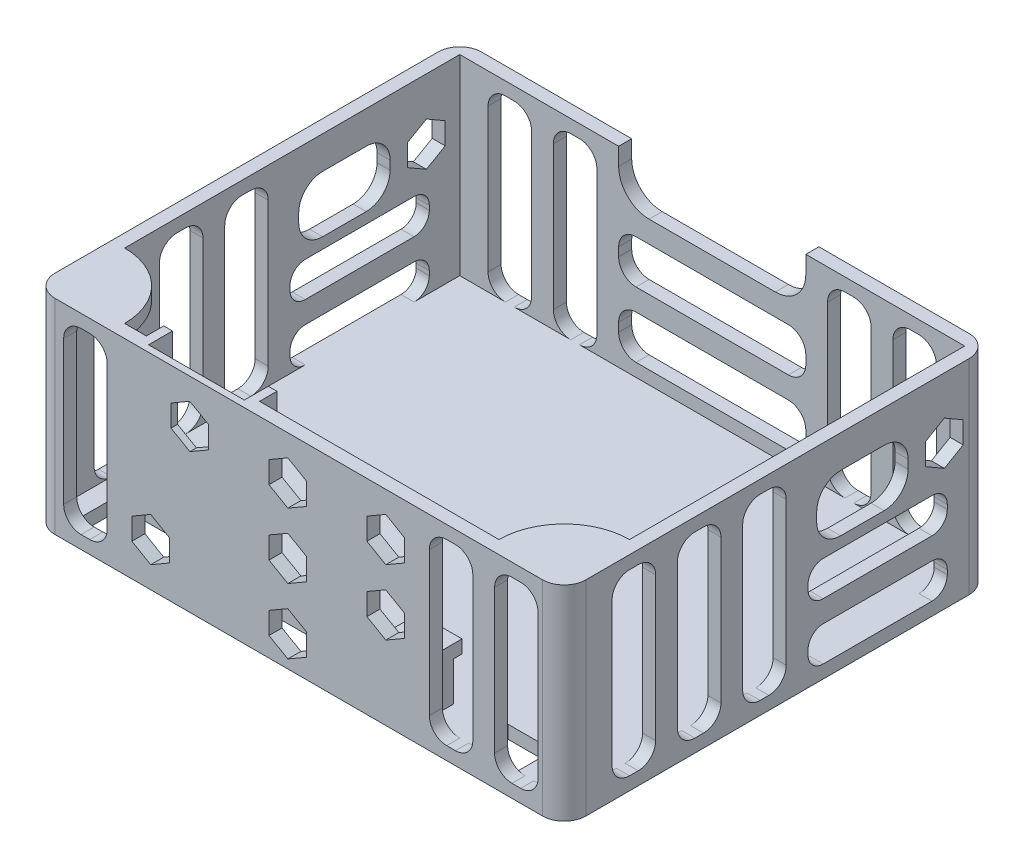
SolidWorks part; units mm, degrees
ref_plane "Front Plane" through (0, 0, 0) normal (0, 0, 1) x (1, 0, 0)
ref_plane "Top Plane" through (0, 0, 0) normal (0, 1, 0) x (1, 0, 0)
ref_plane "Right Plane" through (0, 0, 0) normal (1, 0, 0) x (0, 0, -1)
sketch "Sketch1" plane through (0, 0, 0) normal (0, 1, 0) x (1, 0, 0)
  line L1 (-81.2987, -43.7828) -> (-20.2987, -43.7828)
  line L2 (-81.2987, -43.7828) -> (-81.2987, 5.2172)
  line L3 (-81.2987, 5.2172) -> (-20.2987, 5.2172)
  line L4 (-20.2987, -43.7828) -> (-20.2987, 5.2172)
  dimension "D1" = 61
  dimension "D2" = 49
extrude "Boss-Extrude1" add sketch "Sketch1" along normal blind 23.5
sketch "Sketch2" plane through (0, 23.5, 0) normal (0, 1, 0) x (1, 0, 0)
  line L0 (-81.2987, 5.2172) -> (-81.2987, -43.7828) construction
  line L1 (-79.7987, 3.7172) -> (-21.7987, 3.7172)
  line L2 (-79.7987, 3.7172) -> (-79.7987, -42.2828)
  line L3 (-79.7987, -42.2828) -> (-21.7987, -42.2828)
  line L4 (-21.7987, 3.7172) -> (-21.7987, -42.2828)
  line L5 (-81.2987, -43.7828) -> (-20.2987, -43.7828) construction
  line L6 (-20.2987, -43.7828) -> (-20.2987, 5.2172) construction
  line L7 (-20.2987, 5.2172) -> (-81.2987, 5.2172) construction
  dimension "D1" = 1.5
  dimension "D2" = 1.5
  dimension "D3" = 1.5
  dimension "D4" = 1.5
extrude "Cut-Extrude1" cut sketch "Sketch2" against normal blind 22
sketch "Sketch3" plane through (0, 1.5, 0) normal (0, 1, 0) x (1, 0, 0)
  line L0 (-79.7987, -42.2828) -> (-21.7987, -42.2828) construction
  line L1 (-58.5387, -39.2828) -> (-42.5387, -39.2828)
  line L2 (-58.5387, -39.2828) -> (-58.5387, -42.2828)
  line L3 (-58.5387, -42.2828) -> (-42.5387, -42.2828)
  line L4 (-42.5387, -39.2828) -> (-42.5387, -42.2828)
  line L5 (-21.7987, -42.2828) -> (-21.7987, 3.7172) construction
  line L6 (-32.3987, -38.1328) -> (-27.1987, -38.1328)
  line L7 (-32.3987, -38.1328) -> (-32.3987, -42.2828)
  line L8 (-32.3987, -42.2828) -> (-27.1987, -42.2828)
  line L9 (-27.1987, -38.1328) -> (-27.1987, -42.2828)
  line L10 (-65.5387, -37.2828) -> (-77.5387, -37.2828)
  line L11 (-65.5387, -37.2828) -> (-65.5387, -42.2828)
  line L12 (-65.5387, -42.2828) -> (-77.5387, -42.2828)
  line L13 (-77.5387, -37.2828) -> (-77.5387, -42.2828)
  dimension "D1" = 3
  dimension "D2" = 5.4
  dimension "D3" = 5.2
  dimension "D4" = 10.14
  dimension "D5" = 4.15
  dimension "D6" = 7
  dimension "D7" = 12
  dimension "D8" = 16
  dimension "D9" = 5
extrude "Cut-Extrude2" cut sketch "Sketch3" against normal blind 1.5
sketch "Sketch4" plane through (0, 23.5, 0) normal (0, 1, 0) x (1, 0, 0)
  line L0 (-20.2987, 5.2172) -> (-81.2987, 5.2172) construction
  line L1 (-61.5487, 5.2172) -> (-40.0487, 5.2172)
  line L2 (-61.5487, 5.2172) -> (-61.5487, 3.7172)
  line L3 (-61.5487, 3.7172) -> (-40.0487, 3.7172)
  line L4 (-40.0487, 5.2172) -> (-40.0487, 3.7172)
  line L5 (-21.7987, 3.7172) -> (-79.7987, 3.7172) construction
  dimension "D1" = 18.25
  dimension "D2" = 18.25
extrude "Cut-Extrude3" cut sketch "Sketch4" against normal blind 5.5
sketch "Sketch5" plane through (-81.2987, 0, 0) normal (-1, 0, 0) x (0, 0, 1)
  line L0 (-5.2172, 23.5) -> (43.7828, 23.5) construction
  line L1 (4.2828, 19.75) -> (14.7828, 19.75)
  line L2 (4.2828, 19.75) -> (4.2828, 13.25)
  line L3 (4.2828, 13.25) -> (14.7828, 13.25)
  line L4 (14.7828, 19.75) -> (14.7828, 13.25)
  dimension "D1" = 10.5
  dimension "D2" = 6.5
  dimension "D3" = 3.75
  dimension "D4" = 8
extrude "Cut-Extrude6" cut sketch "Sketch5" against normal blind 61
sketch "Sketch8" plane through (0, 1.5, 0) normal (0, 1, 0) x (1, 0, 0)
  line L0 (-42.5387, -42.2828) -> (-32.3987, -42.2828) construction
  line L1 (-37.5387, -42.2828) -> (-42.5387, -42.2828)
  line L2 (-37.5387, -42.2828) -> (-37.5387, -39.2828)
  line L3 (-37.5387, -39.2828) -> (-42.5387, -39.2828)
  line L4 (-42.5387, -42.2828) -> (-42.5387, -39.2828)
  line L6 (-58.5387, -42.2828) -> (-63.5387, -42.2828)
  line L7 (-58.5387, -42.2828) -> (-58.5387, -39.2828)
  line L8 (-58.5387, -39.2828) -> (-63.5387, -39.2828)
  line L9 (-63.5387, -42.2828) -> (-63.5387, -39.2828)
  dimension "D1" = 5
  dimension "D2" = 5
extrude "Boss-Extrude2" add sketch "Sketch8" along normal blind 6
sketch "Sketch9" plane through (0, 0, 39.2828) normal (0, 0, -1) x (-1, 0, 0)
  line L0 (37.5387, 7.5) -> (42.5387, 7.5) construction
  line L1 (37.5387, 7.5) -> (42.5387, 7.5)
  line L2 (37.5387, 7.5) -> (37.5387, 6)
  line L3 (37.5387, 6) -> (42.5387, 6)
  line L4 (42.5387, 7.5) -> (42.5387, 6)
  line L5 (42.5387, 7.5) -> (42.5387, 1.5) construction
  line L6 (58.5387, 7.5) -> (63.5387, 7.5) construction
  line L7 (58.5387, 7.5) -> (63.5387, 7.5)
  line L8 (58.5387, 7.5) -> (58.5387, 6)
  line L9 (58.5387, 6) -> (63.5387, 6)
  line L10 (63.5387, 7.5) -> (63.5387, 6)
  line L11 (63.5387, 7.5) -> (63.5387, 1.5) construction
  dimension "D1" = 1.5
  dimension "D2" = 1.5
extrude "Boss-Extrude3" add sketch "Sketch9" along normal blind 1
sketch "Sketch10" plane through (0, 0, 42.2828) normal (0, 0, -1) x (-1, 0, 0)
  line L0 (79.7987, 23.5) -> (21.7987, 23.5) construction
  line L1 (57.7987, 23.5) -> (68.7987, 23.5)
  line L2 (57.7987, 23.5) -> (57.7987, 12.5)
  line L3 (57.7987, 12.5) -> (68.7987, 12.5)
  line L4 (68.7987, 23.5) -> (68.7987, 12.5)
  line L5 (79.7987, 1.5) -> (79.7987, 23.5) construction
  dimension "D1" = 11
  dimension "D2" = 11
  dimension "D3" = 0
  dimension "D4" = 11
extrude "Cut-Extrude8" cut sketch "Sketch10" against normal blind 0.75
sketch "Sketch11" plane through (0, 0, 42.2828) normal (0, 0, -1) x (-1, 0, 0)
  line L1 (57.7987, 23.5) -> (56.7987, 23.5)
  line L2 (57.7987, 23.5) -> (57.7987, 11.5)
  line L3 (57.7987, 11.5) -> (56.7987, 11.5)
  line L4 (56.7987, 23.5) -> (56.7987, 11.5)
  line L5 (68.7987, 12.5) -> (57.7987, 12.5)
  line L6 (68.7987, 12.5) -> (68.7987, 11.5)
  line L7 (68.7987, 11.5) -> (57.7987, 11.5)
  line L8 (57.7987, 12.5) -> (57.7987, 11.5)
  line L9 (68.7987, 23.5) -> (69.7987, 23.5)
  line L10 (68.7987, 23.5) -> (68.7987, 11.5)
  line L11 (68.7987, 11.5) -> (69.7987, 11.5)
  line L12 (69.7987, 23.5) -> (69.7987, 11.5)
  line M8 (68.7987, 12.5) -> (57.7987, 12.5)
  line M30 (79.7987, 23.5) -> (68.7987, 23.5)
  line M31 (68.7987, 23.5) -> (68.7987, 12.5)
  dimension "D1" = 1
  dimension "D2" = 1
  dimension "D3" = 1
  dimension "D4" = 0
extrude "Boss-Extrude4" add sketch "Sketch11" along normal blind 2 contours L7 L6 L2 M8 | L12 L6 L11 M30 M31
sketch "Sketch12" plane through (0, 23.5, 0) normal (0, 1, 0) x (1, 0, 0)
  line L1 (-21.7987, -42.2828) -> (-29.2987, -42.2828)
  line L2 (-21.7987, -42.2828) -> (-21.7987, -34.7828)
  line L3 (-21.7987, -34.7828) -> (-29.2987, -34.7828)
  line L4 (-29.2987, -42.2828) -> (-29.2987, -34.7828)
  line L5 (-79.7987, -42.2828) -> (-72.2987, -42.2828)
  line L6 (-79.7987, -42.2828) -> (-79.7987, -34.7828)
  line L7 (-79.7987, -34.7828) -> (-72.2987, -34.7828)
  line L8 (-72.2987, -42.2828) -> (-72.2987, -34.7828)
  dimension "D1" = 7.5
  dimension "D2" = 7.5
  dimension "D3" = 7.5
  dimension "D4" = 7.5
extrude "Boss-Extrude5" add sketch "Sketch12" against normal blind 1.5
fillet "Fillet1" radius 2.75 1 edges at (-80.5487, 13.25, 14.7828)
fillet "Fillet2" radius 2.75 1 edges at (-80.5487, 19.75, 14.7828)
fillet "Fillet3" radius 2.75 1 edges at (-80.5487, 19.75, 4.2828)
fillet "Fillet4" radius 2.75 1 edges at (-80.5487, 13.25, 4.2828)
fillet "Fillet5" radius 3.5 1 edges at (-40.0487, 18, -4.4672)
fillet "Fillet6" radius 3.5 1 edges at (-61.5487, 18, -4.4672)
fillet "Fillet7" radius 7.5 5 edges at (-29.2987, 22, 38.5328) (-25.5487, 22, 34.7828) (-29.2987, 22.75, 34.7828) (-25.5487, 23.5, 34.7828) (-29.2987, 23.5, 38.5328)
fillet "Fillet8" radius 7.5 5 edges at (-76.0487, 22, 34.7828) (-72.2987, 22, 38.5328) (-72.2987, 22.75, 34.7828) (-72.2987, 23.5, 38.5328) (-76.0487, 23.5, 34.7828)
fillet "Fillet9" radius 2.5 1 edges at (-20.2987, 11.75, -5.2172)
fillet "Fillet10" radius 2.5 1 edges at (-81.2987, 11.75, -5.2172)
fillet "Fillet11" radius 2.5 1 edges at (-81.2987, 11.75, 43.7828)
fillet "Fillet12" radius 2.5 1 edges at (-20.2987, 11.75, 43.7828)
sketch "Sketch13" plane through (-20.2987, 0, 0) normal (1, 0, 0) x (0, 0, -1)
  line L0 (-41.2828, 23.5) -> (2.7172, 23.5) construction
  line L1 (-36.2828, 22) -> (-35.2828, 22)
  line L2 (-38.2828, 20) -> (-38.2828, 3.5)
  line L3 (-36.2828, 1.5) -> (-35.2828, 1.5)
  line L4 (-33.2828, 20) -> (-33.2828, 3.5)
  line L5 (-28.7828, 22) -> (-27.7828, 22)
  line L6 (-30.7828, 20) -> (-30.7828, 3.5)
  line L7 (-28.7828, 1.5) -> (-27.7828, 1.5)
  line L8 (-25.7828, 20) -> (-25.7828, 3.5)
  line L9 (-21.2828, 22) -> (-20.2828, 22)
  line L10 (-23.2828, 20) -> (-23.2828, 3.5)
  line L11 (-21.2828, 1.5) -> (-20.2828, 1.5)
  line L12 (-18.2828, 20) -> (-18.2828, 3.5)
  line L17 (-41.2828, 0) -> (2.7172, 0) construction
  line L18 (-38.2828, 7.5) -> (-38.2828, 6) construction
  arc A0 (-36.2828, 22) -> (-38.2828, 20) centre (-36.2828, 20) ccw
  arc A1 (-35.2828, 22) -> (-33.2828, 20) centre (-35.2828, 20) cw
  arc A2 (-28.7828, 22) -> (-30.7828, 20) centre (-28.7828, 20) ccw
  arc A3 (-27.7828, 22) -> (-25.7828, 20) centre (-27.7828, 20) cw
  arc A4 (-21.2828, 22) -> (-23.2828, 20) centre (-21.2828, 20) ccw
  arc A5 (-20.2828, 22) -> (-18.2828, 20) centre (-20.2828, 20) cw
  arc A6 (-20.2828, 1.5) -> (-18.2828, 3.5) centre (-20.2828, 3.5) ccw
  arc A7 (-23.2828, 3.5) -> (-21.2828, 1.5) centre (-21.2828, 3.5) ccw
  arc A8 (-27.7828, 1.5) -> (-25.7828, 3.5) centre (-27.7828, 3.5) ccw
  arc A9 (-30.7828, 3.5) -> (-28.7828, 1.5) centre (-28.7828, 3.5) ccw
  arc A10 (-35.2828, 1.5) -> (-33.2828, 3.5) centre (-35.2828, 3.5) ccw
  arc A11 (-38.2828, 3.5) -> (-36.2828, 1.5) centre (-36.2828, 3.5) ccw
  point P14 (-38.2828, 22)
  point P23 (-33.2828, 22)
  point P26 (-30.7828, 22)
  point P29 (-25.7828, 22)
  point P32 (-23.2828, 22)
  point P35 (-18.2828, 22)
  dimension "D4" = 2
  dimension "D1" = 5
  dimension "D2" = 5
  dimension "D3" = 5
  dimension "D5" = 2.5
  dimension "D6" = 2.5
  dimension "D8" = 1.5
  dimension "D9" = 1.5
  dimension "D10" = 1.5
  dimension "D12" = 1.5
  dimension "D13" = 1.5
  dimension "D14" = 1.5
  dimension "D16" = 0
extrude "Cut-Extrude10" cut sketch "Sketch13" against normal blind 61
fillet "Fillet13" radius 2.75 1 edges at (-21.0487, 13.25, 14.7828)
fillet "Fillet14" radius 2.75 1 edges at (-21.0487, 19.75, 14.7828)
fillet "Fillet15" radius 2.75 1 edges at (-21.0487, 13.25, 4.2828)
fillet "Fillet16" radius 2.75 1 edges at (-21.0487, 19.75, 4.2828)
sketch "Sketch16" plane through (-20.2987, 0, 0) normal (1, 0, 0) x (0, 0, -1)
  line L0 (-4.2828, 17) -> (-4.2828, 16) construction
  line L1 (-0.1178, 19) -> (-2.2828, 17.75)
  line L2 (-2.2828, 17.75) -> (-2.2828, 15.25)
  line L3 (-2.2828, 15.25) -> (-0.1178, 14)
  line L4 (-0.1178, 14) -> (2.0473, 15.25)
  line L5 (2.0473, 15.25) -> (2.0473, 17.75)
  line L6 (2.0473, 17.75) -> (-0.1178, 19)
  circle A0 centre (-0.1178, 16.5) radius 2.1651 construction
  point P10 (-4.2828, 16.5)
  dimension "D1" = 0
  dimension "D2" = 2.5
  dimension "D3" = 2
extrude "Cut-Extrude11" cut sketch "Sketch16" against normal blind 61
sketch "Sketch19" plane through (0, 0, -5.2172) normal (0, 0, -1) x (-1, 0, 0)
  line L0 (61.5487, 23.5) -> (78.7987, 23.5) construction
  line L1 (66.0487, 22) -> (67.0487, 22)
  line L2 (64.0487, 20) -> (64.0487, 3.5)
  line L3 (66.0487, 1.5) -> (67.0487, 1.5)
  line L4 (69.0487, 20) -> (69.0487, 3.5)
  line L5 (73.5487, 22) -> (74.5487, 22)
  line L6 (71.5487, 20) -> (71.5487, 3.5)
  line L7 (73.5487, 1.5) -> (74.5487, 1.5)
  line L8 (76.5487, 20) -> (76.5487, 3.5)
  line L9 (27.0487, 22) -> (28.0487, 22)
  line L10 (25.0487, 20) -> (25.0487, 3.5)
  line L11 (27.0487, 1.5) -> (28.0487, 1.5)
  line L12 (30.0487, 20) -> (30.0487, 3.5)
  line L13 (34.5487, 22) -> (35.5487, 22)
  line L14 (32.5487, 20) -> (32.5487, 3.5)
  line L15 (34.5487, 1.5) -> (35.5487, 1.5)
  line L16 (37.5487, 20) -> (37.5487, 3.5)
  line L17 (42.0487, 15.5) -> (59.5487, 15.5)
  line L18 (40.0487, 13.5) -> (40.0487, 12.5)
  line L19 (42.0487, 10.5) -> (59.5487, 10.5)
  line L20 (61.5487, 13.5) -> (61.5487, 12.5)
  line L21 (42.0487, 8) -> (59.5487, 8)
  line L22 (40.0487, 6) -> (40.0487, 5)
  line L23 (42.0487, 3) -> (59.5487, 3)
  line L24 (61.5487, 6) -> (61.5487, 5)
  line L25 (22.7987, 0) -> (78.7987, 0) construction
  line L26 (61.5487, 21.5) -> (61.5487, 23.5) construction
  line L27 (40.0487, 21.5) -> (40.0487, 23.5) construction
  line L28 (22.7987, 23.5) -> (40.0487, 23.5) construction
  line L29 (43.5487, 18) -> (58.0487, 18) construction
  arc A0 (25.0487, 3.5) -> (27.0487, 1.5) centre (27.0487, 3.5) ccw
  arc A1 (28.0487, 1.5) -> (30.0487, 3.5) centre (28.0487, 3.5) ccw
  arc A2 (32.5487, 3.5) -> (34.5487, 1.5) centre (34.5487, 3.5) ccw
  arc A3 (35.5487, 1.5) -> (37.5487, 3.5) centre (35.5487, 3.5) ccw
  arc A4 (42.0487, 8) -> (40.0487, 6) centre (42.0487, 6) ccw
  arc A5 (40.0487, 5) -> (42.0487, 3) centre (42.0487, 5) ccw
  arc A6 (59.5487, 8) -> (61.5487, 6) centre (59.5487, 6) cw
  arc A7 (59.5487, 3) -> (61.5487, 5) centre (59.5487, 5) ccw
  arc A8 (64.0487, 3.5) -> (66.0487, 1.5) centre (66.0487, 3.5) ccw
  arc A9 (67.0487, 1.5) -> (69.0487, 3.5) centre (67.0487, 3.5) ccw
  arc A10 (71.5487, 3.5) -> (73.5487, 1.5) centre (73.5487, 3.5) ccw
  arc A11 (74.5487, 1.5) -> (76.5487, 3.5) centre (74.5487, 3.5) ccw
  arc A12 (74.5487, 22) -> (76.5487, 20) centre (74.5487, 20) cw
  arc A13 (73.5487, 22) -> (71.5487, 20) centre (73.5487, 20) ccw
  arc A14 (67.0487, 22) -> (69.0487, 20) centre (67.0487, 20) cw
  arc A15 (66.0487, 22) -> (64.0487, 20) centre (66.0487, 20) ccw
  arc A16 (59.5487, 15.5) -> (61.5487, 13.5) centre (59.5487, 13.5) cw
  arc A17 (59.5487, 10.5) -> (61.5487, 12.5) centre (59.5487, 12.5) ccw
  arc A18 (40.0487, 12.5) -> (42.0487, 10.5) centre (42.0487, 12.5) ccw
  arc A19 (42.0487, 15.5) -> (40.0487, 13.5) centre (42.0487, 13.5) ccw
  arc A20 (35.5487, 22) -> (37.5487, 20) centre (35.5487, 20) cw
  arc A21 (34.5487, 22) -> (32.5487, 20) centre (34.5487, 20) ccw
  arc A22 (28.0487, 22) -> (30.0487, 20) centre (28.0487, 20) cw
  arc A23 (27.0487, 22) -> (25.0487, 20) centre (27.0487, 20) ccw
  point P46 (40.0487, 8)
  point P49 (40.0487, 3)
  point P56 (64.0487, 1.5)
  point P59 (69.0487, 1.5)
  point P62 (71.5487, 1.5)
  point P65 (76.5487, 1.5)
  point P80 (40.0487, 10.5)
  point P83 (40.0487, 15.5)
  point P86 (37.5487, 22)
  point P89 (32.5487, 22)
  point P92 (30.0487, 22)
  point P95 (25.0487, 22)
  dimension "D25" = 2
  dimension "D1" = 1.5
  dimension "D2" = 1.5
  dimension "D3" = 5
  dimension "D4" = 5
  dimension "D5" = 2.5
  dimension "D6" = 1.5
  dimension "D7" = 1.5
  dimension "D8" = 2.5
  dimension "D9" = 2.5
  dimension "D10" = 5
  dimension "D11" = 5
  dimension "D12" = 2.5
  dimension "D13" = 1.5
  dimension "D14" = 1.5
  dimension "D15" = 1.5
  dimension "D16" = 1.5
  dimension "D17" = 2.5
  dimension "D18" = 2.5
  dimension "D19" = 2.5
  dimension "D20" = 2.5
  dimension "D21" = 5
  dimension "D22" = 5
  dimension "D23" = 2.5
  dimension "D24" = 2.5
extrude "Cut-Extrude12" cut sketch "Sketch19" against normal blind 1.5
sketch "Sketch20" plane through (-20.2987, 0, 0) normal (1, 0, 0) x (0, 0, -1)
  line L0 (-41.2828, 0) -> (2.7172, 0) construction
  line L1 (-1.5328, 1.5) -> (-14.0328, 1.5)
  line L2 (0.2172, 3.25) -> (0.2172, 3.75)
  line L3 (-1.5328, 5.5) -> (-14.0328, 5.5)
  line L4 (-15.7828, 3.25) -> (-15.7828, 3.75)
  line L5 (-1.5328, 8) -> (-14.0328, 8)
  line L6 (0.2172, 9.75) -> (0.2172, 10.25)
  line L7 (-1.5328, 12) -> (-14.0328, 12)
  line L8 (-15.7828, 9.75) -> (-15.7828, 10.25)
  line L9 (2.7172, 0) -> (2.7172, 23.5) construction
  line L10 (-18.2828, 3.5) -> (-18.2828, 20) construction
  arc A0 (-14.0328, 12) -> (-15.7828, 10.25) centre (-14.0328, 10.25) ccw
  arc A1 (-14.0328, 8) -> (-15.7828, 9.75) centre (-14.0328, 9.75) cw
  arc A2 (0.2172, 10.25) -> (-1.5328, 12) centre (-1.5328, 10.25) ccw
  arc A3 (-1.5328, 8) -> (0.2172, 9.75) centre (-1.5328, 9.75) ccw
  arc A4 (0.2172, 3.75) -> (-1.5328, 5.5) centre (-1.5328, 3.75) ccw
  arc A5 (-1.5328, 1.5) -> (0.2172, 3.25) centre (-1.5328, 3.25) ccw
  arc A6 (-14.0328, 5.5) -> (-15.7828, 3.75) centre (-14.0328, 3.75) ccw
  arc A7 (-14.0328, 1.5) -> (-15.7828, 3.25) centre (-14.0328, 3.25) cw
  point P16 (-15.7828, 12)
  point P19 (-15.7828, 8)
  point P30 (-15.7828, 5.5)
  point P33 (-15.7828, 1.5)
  dimension "D9" = 1.75
  dimension "D10" = 1.75
  dimension "D1" = 1.5
  dimension "D2" = 2.5
  dimension "D3" = 4
  dimension "D4" = 4
  dimension "D5" = 2.5
  dimension "D6" = 2.5
  dimension "D7" = 2.5
  dimension "D8" = 2.5
extrude "Cut-Extrude14" cut sketch "Sketch20" against normal blind 61
sketch "Sketch21" plane through (0, 0, 43.0328) normal (0, 0, -1) x (-1, 0, 0)
  line L1 (63.2267, 15.2845) -> (65.784, 16.7609)
  line L2 (65.784, 16.7609) -> (65.784, 19.7138)
  line L3 (65.784, 19.7138) -> (63.2267, 21.1902)
  line L4 (63.2267, 21.1902) -> (60.6695, 19.7138)
  line L5 (60.6695, 19.7138) -> (60.6695, 16.7609)
  line L6 (60.6695, 16.7609) -> (63.2267, 15.2845)
  circle A0 centre (63.2267, 18.2373) radius 2.5572 construction
  point P1 (58.7555, 8.9727)
sketch "Sketch22" plane through (0, 0, 42.2828) normal (0, 0, -1) x (-1, 0, 0)
  line L0 (56.7987, 23.5) -> (29.2987, 23.5) construction
  line L1 (75.7987, 22) -> (74.7987, 22)
  line L2 (77.7987, 20) -> (77.7987, 3.5)
  line L3 (75.7987, 1.5) -> (74.7987, 1.5)
  line L4 (72.7987, 20) -> (72.7987, 3.5)
  line L5 (26.2987, 22) -> (25.2987, 22)
  line L6 (28.2987, 20) -> (28.2987, 3.5)
  line L7 (26.2987, 1.5) -> (25.2987, 1.5)
  line L8 (23.2987, 20) -> (23.2987, 3.5)
  line L9 (33.7987, 22) -> (32.7987, 22)
  line L10 (35.7987, 20) -> (35.7987, 3.5)
  line L11 (33.7987, 1.5) -> (32.7987, 1.5)
  line L12 (30.7987, 20) -> (30.7987, 3.5)
  line L13 (78.7987, 23.5) -> (22.7987, 23.5) construction
  line L14 (27.1987, 1.5) -> (21.7987, 1.5) construction
  line L15 (37.5387, 1.5) -> (32.3987, 1.5) construction
  line L16 (21.7987, 1.5) -> (21.7987, 22) construction
  line L17 (79.7987, 1.5) -> (79.7987, 22) construction
  line L18 (79.7987, 1.5) -> (77.5387, 1.5) construction
  arc A0 (32.7987, 1.5) -> (30.7987, 3.5) centre (32.7987, 3.5) cw
  arc A1 (25.2987, 1.5) -> (23.2987, 3.5) centre (25.2987, 3.5) cw
  arc A2 (25.2987, 22) -> (23.2987, 20) centre (25.2987, 20) ccw
  arc A3 (33.7987, 22) -> (35.7987, 20) centre (33.7987, 20) cw
  arc A4 (32.7987, 22) -> (30.7987, 20) centre (32.7987, 20) ccw
  arc A5 (26.2987, 22) -> (28.2987, 20) centre (26.2987, 20) cw
  arc A6 (28.2987, 3.5) -> (26.2987, 1.5) centre (26.2987, 3.5) cw
  arc A7 (35.7987, 3.5) -> (33.7987, 1.5) centre (33.7987, 3.5) cw
  arc A8 (75.7987, 22) -> (77.7987, 20) centre (75.7987, 20) cw
  arc A9 (74.7987, 22) -> (72.7987, 20) centre (74.7987, 20) ccw
  arc A10 (74.7987, 1.5) -> (72.7987, 3.5) centre (74.7987, 3.5) cw
  arc A11 (77.7987, 3.5) -> (75.7987, 1.5) centre (75.7987, 3.5) cw
  point P28 (30.7987, 1.5)
  point P31 (23.2987, 1.5)
  point P42 (28.2987, 1.5)
  point P45 (35.7987, 1.5)
  point P48 (77.7987, 22)
  point P51 (72.7987, 22)
  dimension "D13" = 2
  dimension "D1" = 1.5
  dimension "D2" = 1.5
  dimension "D3" = 0
  dimension "D4" = 0
  dimension "D5" = 5
  dimension "D6" = 5
  dimension "D7" = 1.5
  dimension "D8" = 2.5
  dimension "D9" = 5
  dimension "D10" = 1.5
  dimension "D11" = 2
  dimension "D12" = 0
extrude "Cut-Extrude15" cut sketch "Sketch22" against normal blind 1.5
sketch "Sketch23" plane through (0, 0, 43.0328) normal (0, 0, -1) x (-1, 0, 0)
  line L0 (56.7987, 23.5) -> (29.2987, 23.5) construction
  line L1 (40.7987, 16) -> (42.9638, 17.25)
  line L2 (42.9638, 17.25) -> (42.9638, 19.75)
  line L3 (42.9638, 19.75) -> (40.7987, 21)
  line L4 (40.7987, 21) -> (38.6336, 19.75)
  line L5 (38.6336, 19.75) -> (38.6336, 17.25)
  line L6 (38.6336, 17.25) -> (40.7987, 16)
  line L7 (35.7987, 3.5) -> (35.7987, 20) construction
  line L8 (52.0487, 16) -> (54.2138, 17.25)
  line L9 (54.2138, 17.25) -> (54.2138, 19.75)
  line L10 (54.2138, 19.75) -> (52.0487, 21)
  line L11 (52.0487, 21) -> (49.8836, 19.75)
  line L12 (49.8836, 19.75) -> (49.8836, 17.25)
  line L13 (49.8836, 17.25) -> (52.0487, 16)
  line L14 (63.2987, 16) -> (65.4638, 17.25)
  line L15 (65.4638, 17.25) -> (65.4638, 19.75)
  line L16 (65.4638, 19.75) -> (63.2987, 21)
  line L17 (63.2987, 21) -> (61.1336, 19.75)
  line L18 (61.1336, 19.75) -> (61.1336, 17.25)
  line L19 (61.1336, 17.25) -> (63.2987, 16)
  line L20 (52.0487, 8.5) -> (54.2138, 9.75)
  line L21 (54.2138, 9.75) -> (54.2138, 12.25)
  line L22 (54.2138, 12.25) -> (52.0487, 13.5)
  line L23 (52.0487, 13.5) -> (49.8836, 12.25)
  line L24 (49.8836, 12.25) -> (49.8836, 9.75)
  line L25 (49.8836, 9.75) -> (52.0487, 8.5)
  line L32 (52.0487, 1) -> (54.2138, 2.25)
  line L33 (54.2138, 2.25) -> (54.2138, 4.75)
  line L34 (54.2138, 4.75) -> (52.0487, 6)
  line L35 (52.0487, 6) -> (49.8836, 4.75)
  line L36 (49.8836, 4.75) -> (49.8836, 2.25)
  line L37 (49.8836, 2.25) -> (52.0487, 1)
  line L44 (40.7987, 8.5) -> (42.9638, 9.75)
  line L45 (42.9638, 9.75) -> (42.9638, 12.25)
  line L46 (42.9638, 12.25) -> (40.7987, 13.5)
  line L47 (40.7987, 13.5) -> (38.6336, 12.25)
  line L48 (38.6336, 12.25) -> (38.6336, 9.75)
  line L49 (38.6336, 9.75) -> (40.7987, 8.5)
  line L56 (42.9638, 4.75) -> (40.7987, 6) [skipped]
  line L57 (40.7987, 6) -> (38.6336, 4.75) [skipped]
  line L58 (38.6336, 4.75) -> (38.6336, 2.25) [skipped]
  line L59 (38.6336, 2.25) -> (40.7987, 1) [skipped]
  line L60 (40.7987, 1) -> (42.9638, 2.25) [skipped]
  line L61 (42.9638, 2.25) -> (42.9638, 4.75) [skipped]
  line L62 (63.2987, 13.5) -> (61.1336, 12.25) [skipped]
  line L63 (65.4638, 12.25) -> (63.2987, 13.5) [skipped]
  line L64 (65.4638, 9.75) -> (65.4638, 12.25) [skipped]
  line L65 (63.2987, 8.5) -> (65.4638, 9.75) [skipped]
  line L66 (61.1336, 9.75) -> (63.2987, 8.5) [skipped]
  line L67 (61.1336, 12.25) -> (61.1336, 9.75) [skipped]
  line L68 (65.4638, 4.75) -> (63.2987, 6) [skipped]
  line L69 (63.2987, 6) -> (61.1336, 4.75) [skipped]
  line L70 (61.1336, 4.75) -> (61.1336, 2.25) [skipped]
  line L71 (61.1336, 2.25) -> (63.2987, 1) [skipped]
  line L72 (63.2987, 1) -> (65.4638, 2.25) [skipped]
  line L73 (65.4638, 2.25) -> (65.4638, 4.75) [skipped]
  circle A0 centre (40.7987, 18.5) radius 2.1651 construction
  dimension "D1" = 2.5
  dimension "D2" = 5
  dimension "D3" = 5
  dimension "D4" = 3
  dimension "D5" = 3
extrude "Cut-Extrude18" cut sketch "Sketch23" against normal blind 1.5 and the other way blind 1.5
sketch "Sketch24" plane through (0, 0, 42.2828) normal (0, 0, -1) x (-1, 0, 0)
  line L0 (77.5387, 0) -> (65.5387, 0) construction
  line L1 (67.7987, 7.5) -> (65.6336, 6.25)
  line L2 (65.6336, 6.25) -> (65.6336, 3.75)
  line L3 (65.6336, 3.75) -> (67.7987, 2.5)
  line L4 (67.7987, 2.5) -> (69.9638, 3.75)
  line L5 (69.9638, 3.75) -> (69.9638, 6.25)
  line L6 (69.9638, 6.25) -> (67.7987, 7.5)
  line L7 (72.7987, 20) -> (72.7987, 3.5) construction
  circle A0 centre (67.7987, 5) radius 2.1651 construction
  point P1 (62.673, 10.4841)
  dimension "D1" = 2.5
  dimension "D2" = 5
  dimension "D3" = 5
extrude "Cut-Extrude19" cut sketch "Sketch24" against normal blind 1.5
